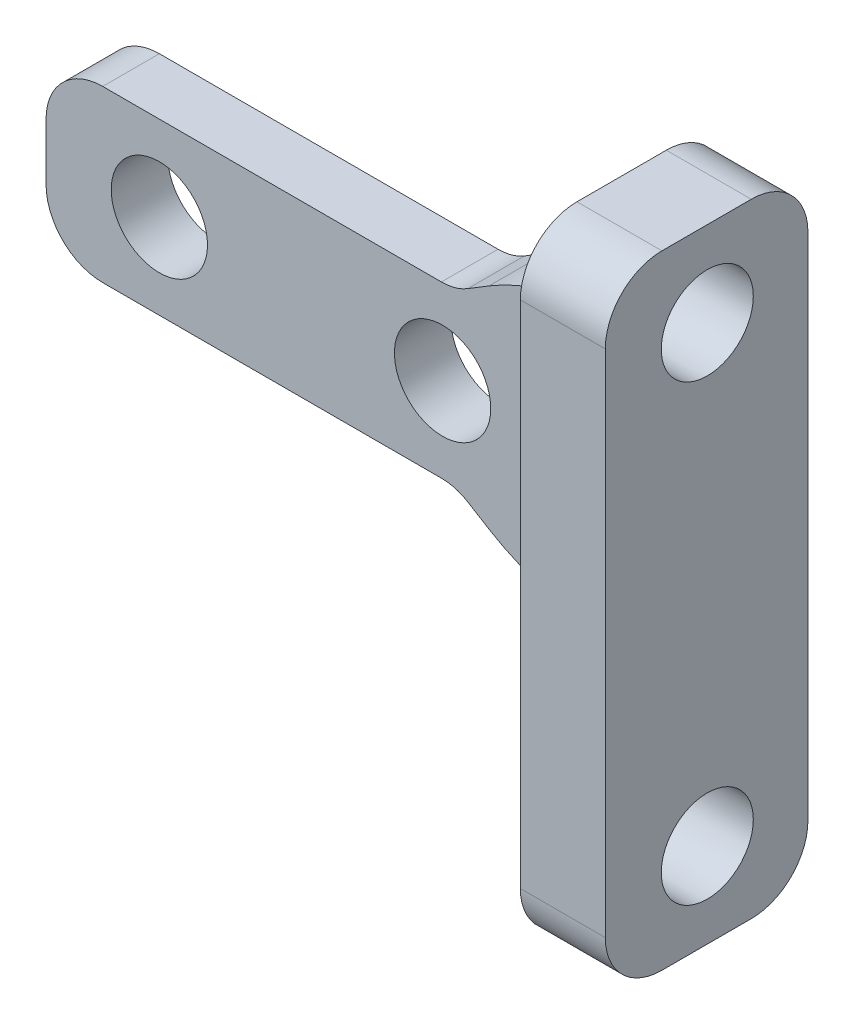
SolidWorks part; units mm, degrees
ref_plane "Front Plane" through (0, 0, 0) normal (0, 0, 1) x (1, 0, 0)
ref_plane "Top Plane" through (0, 0, 0) normal (0, 1, 0) x (1, 0, 0)
ref_plane "Right Plane" through (0, 0, 0) normal (1, 0, 0) x (0, 0, -1)
sketch "Sketch1" plane through (0, 0, 0) normal (0, 0, 1) x (1, 0, 0)
  line L0 (0, 0) -> (10, 0) construction
  line L3 (-4, 3) -> (-4, -3)
  line L4 (-4, -3) -> (9.9583, -3)
  line L7 (20.9, -11) -> (20.9, 11)
  line L10 (9.9583, 3) -> (-4, 3)
  line L11 (20.9, 11.7) -> (20.9, 0.8414) construction
  line L12 (20.9, 11) -> (17.9, 11)
  line L13 (20.9, 11) -> (20.9, -11)
  line L14 (20.9, -11) -> (17.9, -11)
  line L15 (17.9, 11) -> (17.9, -11)
  line L16 (15.5807, 4.83) -> (17.9, 4.83)
  line L17 (-5.099, 3) -> (-15, 3) construction
  line L18 (15.5807, -4.83) -> (17.9, -4.83)
  line L20 (10.8914, 3.2626) -> (11.6424, 3.7217)
  line L22 (10.8914, -3.2626) -> (11.6424, -3.7217)
  circle A2 centre (0, 0) radius 1.5 construction
  circle A3 centre (10, 0) radius 1.5 construction
  arc A4 (9.9583, 3) -> (10.8914, 3.2626) centre (9.9583, 4.7891) ccw
  arc A5 (9.9583, -3) -> (10.8914, -3.2626) centre (9.9583, -4.7891) cw
  arc A6 (11.6424, 3.7217) -> (15.5807, 4.83) centre (15.5807, -2.7214) cw
  arc A7 (11.6424, -3.7217) -> (15.5807, -4.83) centre (15.5807, 2.7214) ccw
  point P7 (-4, 0)
  point P17 (20.9, 0)
  point P18 (13.0082, 4.5565)
  dimension "D2" = 3
  dimension "D1" = 10
  dimension "D3" = 22
  dimension "D5" = 4
  dimension "D6" = 3
extrude "Boss-Extrude1" add sketch "Sketch1" along normal blind 2 contours L15 A4 L10 L3 L4 | L15 L7 region at (8.0458, 0, 0) region at (19.4, 0, 0)
extrude "Boss-Extrude2" add sketch "Sketch1<3>" along normal up to surface (7.154 mm away) contours L12 L15 L14 L7 region at (19.4, 0, 0)
sketch "Sketch1<3>" plane through (0, 0, 0) normal (0, 0, 1) x (1, 0, 0) same geometry as "Sketch1"
hole_wizard "M3 Clearance Hole1" positions "Sketch2" profile "Sketch4" hole size "M3" standard "ANSI Metric" end condition through all
sketch "Sketch2" plane through (0, 0, 2) normal (0, 0, 1) x (1, 0, 0)
  point P0 (0, 0)
  point P5 (10, 0)
sketch "Sketch4" plane through (0, 0, 2) normal (1, 0, 0) x (0, -1, 0)
  line L0 (0, 0) -> (0, 2)
  line L1 (0, 2) -> (1.7, 2)
  line L2 (1.7, 2) -> (1.7, 0)
  line L5 (1.7, 0) -> (0, 0)
  line L11 (0, -6.35) -> (0, 107.95) construction
  dimension "Thru Hole Dia." = 3.4
  dimension "Thru Hole Depth" = 2
fillet "Fillet1" radius 2 6 edges at (-4, 3, 1) (-4, -3, 1) (19.4, -11, 7.154) (19.4, 11, 7.154) (19.4, 11, 0) (19.4, -11, 0)
sketch "Sketch6" plane through (20.9, 0, 0) normal (1, 0, 0) x (0, 0, -1)
  line L0 (0, -11) -> (0, 11) construction
  line L1 (-3.554, 8) -> (-3.554, -8)
  line L3 (0, 11) -> (0, -11) construction
  circle A0 centre (-3.554, -8) radius 1.625
  circle A1 centre (-3.554, 8) radius 1.625
  point P5 (0, 0)
  point P11 (-3.554, 0)
  dimension "D2" = 3.25
  dimension "D3" = 3.554
  dimension "D4" = 16
extrude "Cut-Extrude1" cut sketch "Sketch6" against normal blind 7.5 contours A0 | A1 region at (20.9, -6.8835, 2.4375) region at (20.9, 9.1165, 4.6705)
fillet "Fillet2" radius 1 1 edges at (17.9, 0, 2)
sketch "Sketch7" plane through (0, 0, 0) normal (0, 1, 0) x (1, 0, 0)
  line L0 (13.4, 0) -> (19.4, -7.154)
  line L4 (20.9, -5.154) -> (20.9, -2) construction
  line L5 (9.9583, 0) -> (-4, 0) construction
  line L6 (20.9, -7.154) -> (17.9, -7.154) construction
  line L7 (20.9, -5.154) -> (20.9, -2) construction
  point P2 (0, 0)
  point P3 (17.9, -4.2349)
  point P4 (20.9, -4.9109)
  point P5 (20.9, -7.154)
  point P6 (17.9, -3.3008)
  point P8 (12.7616, -2)
  point P9 (0, 0)
  point P13 (0, 0)
  point P15 (0, 0)
  point P17 (0, 0)
  point P18 (19.3355, -7.154)
  dimension "D1" = 1.5
  dimension "D2" = 7.5
chamfer "Chamfer1" distance 0.5 angle 45 2 edges at (17.9, -4.83, 1.5) (17.9, 4.83, 1.5)
